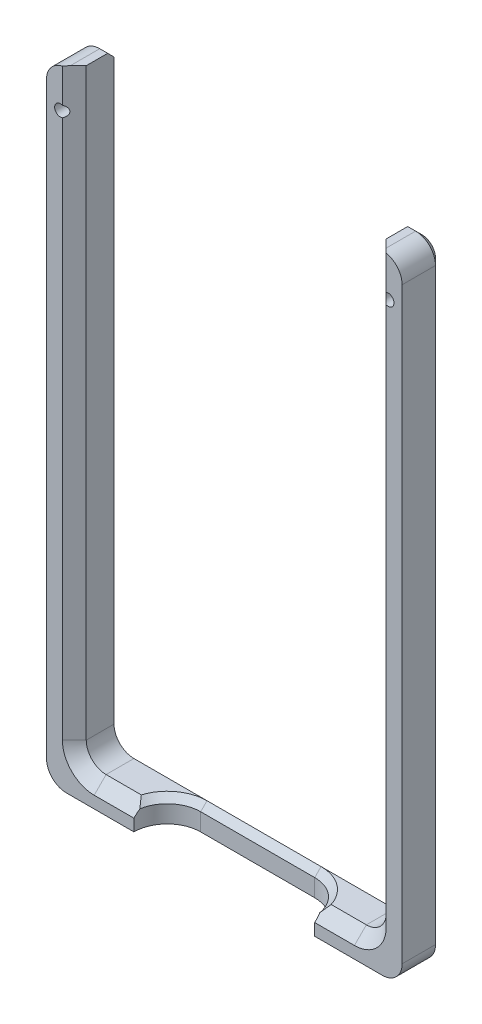
SolidWorks part; units mm, degrees
ref_plane "Front Plane" through (0, 0, 0) normal (0, 0, 1) x (1, 0, 0)
ref_plane "Top Plane" through (0, 0, 0) normal (0, 1, 0) x (1, 0, 0)
ref_plane "Right Plane" through (0, 0, 0) normal (1, 0, 0) x (0, 0, -1)
sketch "Sketch1" plane through (0, 0, 0) normal (0, 0, 1) x (1, 0, 0)
  line L1 (-44.75, -78) -> (44.75, -78)
  line L2 (-44.75, -78) -> (-44.75, 78)
  line L3 (-44.75, 78) -> (44.75, 78)
  line L4 (44.75, -78) -> (44.75, 78)
  line L5 (0, 78) -> (0, -78) construction
  line L6 (-44.75, 0) -> (44.75, 0) construction
  point P0 (0, 0)
  dimension "D1" = 89.5
  dimension "D2" = 156
sketch "Sketch2" plane through (0, 0, 0) normal (0, 0, 1) x (1, 0, 0)
  line L0 (-44.75, 78) -> (-37.75, 78)
  line L1 (-44.75, 78) -> (44.75, 78) construction
  line L2 (-37.75, 78) -> (-37.75, -74)
  line L3 (-37.75, -74) -> (37.75, -74)
  line L4 (37.75, -74) -> (37.75, 78)
  line L5 (37.75, 78) -> (44.75, 78)
  line L6 (44.75, 78) -> (44.75, -80)
  line L7 (44.75, -80) -> (-44.75, -80)
  line L8 (-44.75, -80) -> (-44.75, 78)
  line L9 (-44.75, -78) -> (44.75, -78) construction
  dimension "D1" = 2
  dimension "D2" = 7
  dimension "D3" = 152
extrude "Boss-Extrude1" add sketch "Sketch2" along normal blind 10
sketch "Sketch4" plane through (0, 0, 10) normal (0, 0, 1) x (1, 0, 0)
  line L0 (0, -1000) -> (0, 49000) construction
  line L1 (-44.75, 78) -> (-37.75, 78) construction
  circle A0 centre (-41.25, 68) radius 1.45
  circle A1 centre (41.25, 68) radius 1.45
  point P7 (-41.25, 78)
  dimension "D1" = 2.9
  dimension "D2" = 10
extrude "Cut-Extrude2" cut sketch "Sketch4" against normal through all
fillet "Fillet3" radius 5 2 edges at (37.75, -74, 5) (-37.75, -74, 5)
chamfer "Chamfer1" distance 3 angle 45 5 edges at (-37.75, 4.5, 10) (37.75, 4.5, 10) (36.2855, -72.5355, 10) (0, -74, 10) (-36.2855, -72.5355, 10)
fillet "Fillet1" radius 5 2 edges at (44.75, 78, 5) (-44.75, 78, 5)
fillet "Fillet2" radius 5 2 edges at (44.75, -80, 5) (-44.75, -80, 5)
chamfer "Chamfer2" distance 1.6 angle 45 9 edges at (-38.75, 78, 0) (38.75, 78, 0) (-43.2855, 76.5355, 0) (43.2855, 76.5355, 0) (-44.75, -1, 0) (44.75, -1, 0) (-43.2855, -78.5355, 0) (43.2855, -78.5355, 0) (0, -80, 0)
sketch "Sketch3" plane through (0, -80, 0) normal (0, -1, 0) x (1, 0, 0)
  line L0 (-14.35, 10) -> (14.35, 10) construction
  line L1 (-39.75, 10) -> (39.75, 10) construction
  line L2 (-14.35, 18.4) -> (14.35, 18.4)
  line L3 (-14.35, 1.6) -> (14.35, 1.6)
  line L5 (44.75, 0) -> (-44.75, 0) construction
  arc A0 (-14.35, 18.4) -> (-14.35, 1.6) centre (-14.35, 10) ccw
  arc A1 (14.35, 1.6) -> (14.35, 18.4) centre (14.35, 10) ccw
  point P4 (0, 10)
  point P9 (20.809, 3.059)
  point P15 (-22.75, 10)
  dimension "D1" = 15
  dimension "D2" = 1.6
extrude "Cut-Extrude1" cut sketch "Sketch3" against normal through all
chamfer "Chamfer3" distance 1.6 angle 45 3 edges at (-19.1124, -74, 3.0805) (19.1124, -74, 3.0805) (0, -74, 1.6)
